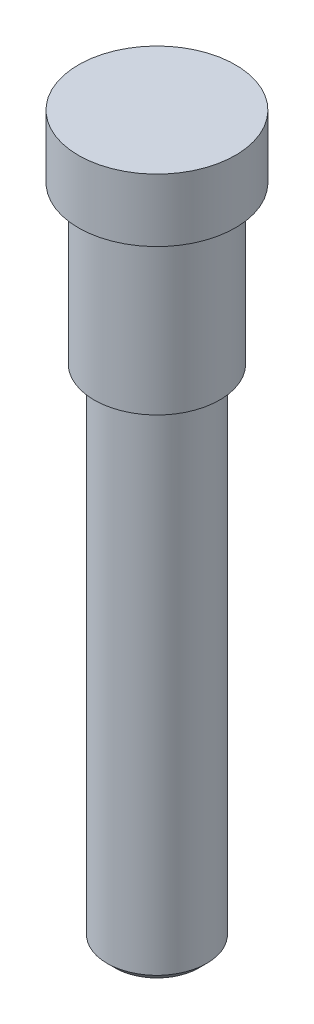
SolidWorks part; units mm, degrees
ref_plane "Front Plane" through (0, 0, 0) normal (0, 0, 1) x (1, 0, 0)
ref_plane "Top Plane" through (0, 0, 0) normal (0, 1, 0) x (1, 0, 0)
ref_plane "Right Plane" through (0, 0, 0) normal (1, 0, 0) x (0, 0, -1)
ref_axis "X-Axis" through (-88.99, 0, 0) along (1, 0, 0)
ref_axis "Y-Axis" through (0, 55, 0) along (0, -1, 0)
ref_axis "Z-Axis" through (0, 0, 55) along (0, 0, -1)
sketch "Sketch1" plane through (0, 0, 0) normal (0, 0, 1) x (1, 0, 0)
  line L0 (0, 55) -> (0, -55) construction
  line L1 (0, -16) -> (-3.175, -16)
  line L4 (-3.175, -16) -> (-3.175, 16)
  line L5 (-88.99, 0) -> (88.99, 0) construction
  line L6 (-3.175, 16) -> (-4, 16)
  line L7 (0, -16) -> (0, 18.8253)
  line L9 (-4, 16) -> (-4, 26)
  line L10 (-4, 26) -> (-5, 26)
  line L11 (0, 18.8253) -> (0, 30)
  line L12 (0, 30) -> (-5, 30)
  line L13 (-5, 26) -> (-5, 30)
  point P14 (0, 0)
  point P15 (0, -26.1742)
  dimension "D1" = 3.175
  dimension "D2" = 4
  dimension "D3" = 5
  dimension "D4" = 46
  dimension "D5" = 10
  dimension "D6" = 4
  dimension "D7" = 30
revolve "Revolve1" add sketch "Sketch1" angle 360 about axis through (0, 55, 0) along (0, -1, 0)
chamfer "Chamfer5" distance 0.5 angle 45 1 edges at (0, -16, 3.175)
